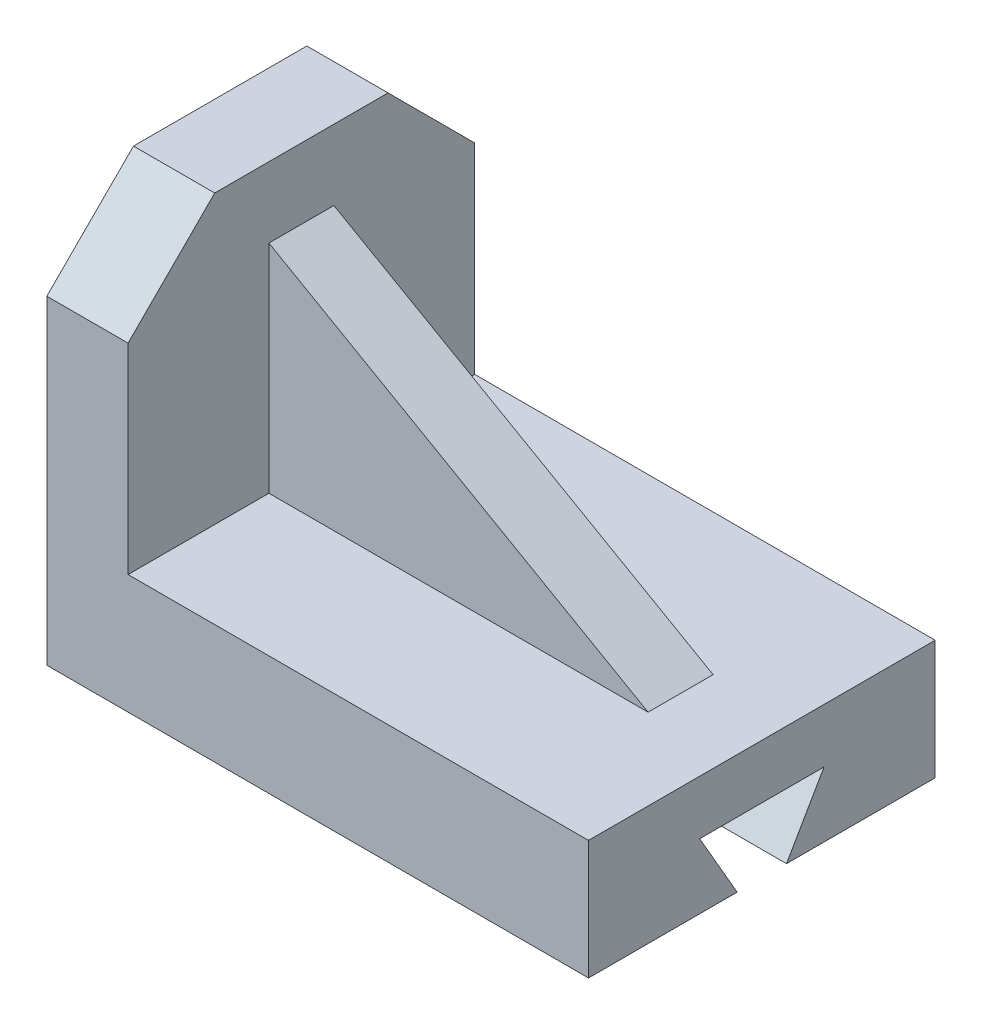
SolidWorks part; units mm, degrees
ref_plane "Front Plane" through (0, 0, 0) normal (0, 0, 1) x (1, 0, 0)
ref_plane "Top Plane" through (0, 0, 0) normal (0, 1, 0) x (1, 0, 0)
ref_plane "Right Plane" through (0, 0, 0) normal (1, 0, 0) x (0, 0, -1)
sketch "Sketch1" plane through (0, 0, 0) normal (0, 1, 0) x (1, 0, 0)
  line L1 (-50, 32) -> (50, 32)
  line L2 (-50, 32) -> (-50, -32)
  line L3 (-50, -32) -> (50, -32)
  line L4 (50, 32) -> (50, -32)
  line L5 (-50, 32) -> (50, -32) construction
  line L6 (-50, -32) -> (50, 32) construction
  point P0 (0, 0)
  dimension "D1" = 100
  dimension "D2" = 64
extrude "Boss-Extrude1" add sketch "Sketch1" along normal blind 22
sketch "Sketch2" plane through (50, 0, 0) normal (1, 0, 0) x (0, 0, -1)
  line L0 (0, 0) -> (0, 22) construction
  line L1 (-32, 22) -> (32, 22) construction
  line L2 (-11.48, 12) -> (-4.5518, 0)
  line L3 (11.48, 12) -> (4.5518, 0)
  line L4 (-32, 0) -> (32, 0) construction
  line L5 (-11.48, 12) -> (11.48, 12)
  dimension "D1" = 60
extrude "Cut-Extrude1" cut sketch "Sketch2" against normal through all and the other way through all
sketch "Sketch4" plane through (0, 22, 0) normal (0, 1, 0) x (1, 0, 0)
  line L0 (-50, -32) -> (50, -32) construction
  line L1 (-50, 32) -> (-35, 32)
  line L2 (-50, 32) -> (-50, -32)
  line L3 (-50, -32) -> (-35, -32)
  line L4 (-35, 32) -> (-35, -32)
  dimension "D1" = 15
extrude "Boss-Extrude2" add sketch "Sketch4" along normal blind 53
fillet "Chamfer1" radius 16 1 edges at (-42.5, 75, 32) type face fillet profile chamfer first side face at (-42.5, 75, 0) second side face at (-11.6667, 32.3333, 32)
fillet "Chamfer2" radius 16 1 edges at (-42.5, 75, -32) type face fillet profile chamfer first side face at (-42.5, 75, -8) second side face at (-11.6667, 32.3333, -32)
sketch "Sketch5" plane through (0, 0, 0) normal (0, 0, 1) x (1, 0, 0)
  line L0 (-35, 62) -> (35, 22)
  line L2 (-35, 59) -> (-35, 22) construction
  line L3 (-35, 22) -> (50, 22) construction
  point P7 (0, 0)
  dimension "D1" = 40
  dimension "D2" = 70
rib "Rib1" sketch "Sketch5" sketch "Sketch5" thickness 12 extrusion direction parallel to sketch draft on no parameters "D1"=12
